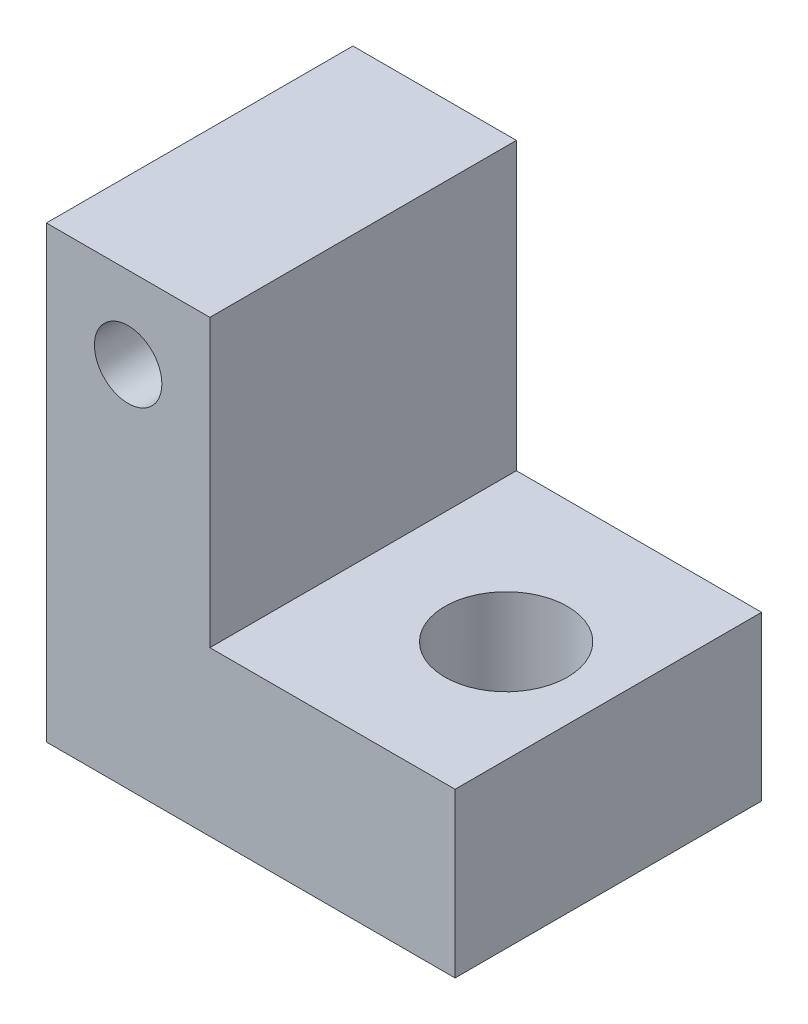
SolidWorks part; units mm, degrees
ref_plane "Piano frontale" through (0, 0, 0) normal (0, 0, 1) x (1, 0, 0)
ref_plane "Piano superiore" through (0, 0, 0) normal (0, 1, 0) x (1, 0, 0)
ref_plane "Piano destro" through (0, 0, 0) normal (1, 0, 0) x (0, 0, -1)
sketch "Schizzo1" plane through (0, 0, 0) normal (0, 0, 1) x (1, 0, 0)
  line L0 (0, 0) -> (-20, 0)
  line L1 (-20, 0) -> (-20, 22)
  line L2 (-20, 22) -> (-12, 22)
  line L3 (-12, 22) -> (-12, 8)
  line L4 (-12, 8) -> (0, 8)
  line L5 (0, 8) -> (0, 0)
  dimension "D1" = 20
  dimension "D2" = 12
  dimension "D3" = 22
  dimension "D4" = 8
extrude "Estrusione-Estrusione1" add sketch "Schizzo1" along normal blind 15
sketch "Schizzo2" plane through (0, 0, 0) normal (0, -1, 0) x (1, 0, 0)
  line L0 (0, 7.5) -> (-20, 7.5) construction
  line L1 (0, 15) -> (0, 0) construction
  line L2 (-20, 15) -> (-20, 0) construction
  circle A0 centre (-5, 7.5) radius 3
  dimension "D1" = 6
  dimension "D2" = 5
extrude "Taglio-Estrusione1" cut sketch "Schizzo2" against normal blind 15
sketch "Schizzo3" plane through (0, 0, 15) normal (0, 0, 1) x (1, 0, 0)
  line L0 (-16, 22) -> (-16, 0) construction
  line L1 (-12, 22) -> (-20, 22) construction
  line L2 (-20, 0) -> (0, 0) construction
  point P6 (-16, 18)
  dimension "D1" = 18
hole_wizard "Foro filettato M4-1" positions "Schizzo5" profile "Schizzo4" tap size "M4" standard "ISO" end condition through all
sketch "Schizzo5" plane through (0, 0, 15) normal (0, 0, 1) x (1, 0, 0)
  point P0 (-16, 18)
cosmetic thread "Filettatura del foro1" parameters "D2"=4
sketch "Schizzo4" plane through (-16, 18, 15) normal (1, 0, 0) x (0, -1, 0)
  line L0 (0, 0) -> (0, 15)
  line L1 (0, 15) -> (1.65, 15)
  line L2 (1.65, 15) -> (1.65, 0)
  line L5 (1.65, 0) -> (0, 0)
  line L11 (0, -6.35) -> (0, 107.95) construction
  dimension "Thru Tap Drill Dia." = 3.3
  dimension "Thru Tap Drill Depth" = 15
